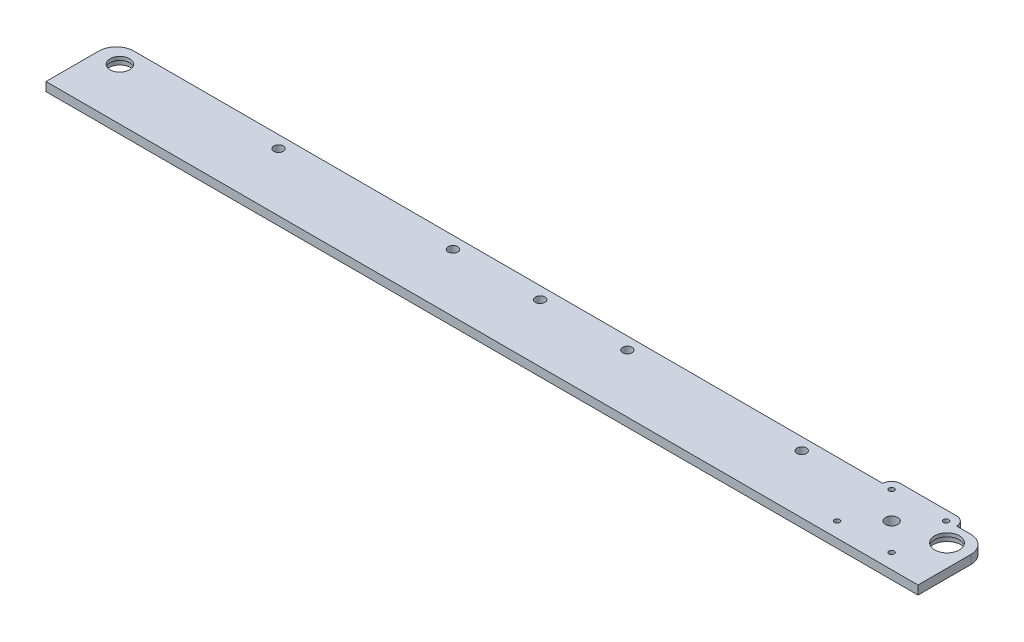
SolidWorks part; units mm, degrees
ref_plane "Front Plane" through (0, 0, 0) normal (0, 0, 1) x (1, 0, 0)
ref_plane "Top Plane" through (0, 0, 0) normal (0, 1, 0) x (1, 0, 0)
ref_plane "Right Plane" through (0, 0, 0) normal (1, 0, 0) x (0, 0, -1)
sketch "Sketch1" plane through (0, 0, 0) normal (0, 1, 0) x (1, 0, 0)
  line L1 (-392.299, 63.778) -> (103.701, 63.778)
  line L2 (-392.299, 63.778) -> (-392.299, 23.778)
  line L3 (-392.299, 23.778) -> (103.701, 23.778)
  line L4 (103.701, 63.778) -> (103.701, 23.778)
  line L8 (-379.799, 53.278) -> (-379.799, 63.778) construction
  line L9 (91.201, 52.778) -> (91.201, 63.778) construction
  line L10 (-144.299, 63.778) -> (-144.299, 183.778) construction
  line L14 (-392.299, 53.278) -> (-392.299, 63.778) construction
  line L15 (-199.299, 183.778) -> (-89.299, 183.778) construction
  line L18 (-392.299, 56.8447) -> (-293.099, 56.8447) construction
  line L20 (-293.099, 56.8447) -> (-193.899, 56.8447) construction
  line L22 (-193.899, 56.8447) -> (-94.699, 56.8447) construction
  line L23 (-94.699, 56.8447) -> (4.501, 56.8447) construction
  line L24 (4.501, 56.8447) -> (103.701, 56.8447) construction
  circle A5 centre (-379.799, 53.278) radius 5.5
  circle A6 centre (91.201, 52.778) radius 7
  circle A10 centre (-293.099, 56.8447) radius 2.7
  circle A11 centre (-193.899, 56.8447) radius 2.7
  circle A12 centre (-94.699, 56.8447) radius 2.7
  circle A13 centre (4.501, 56.8447) radius 2.7
  circle A14 centre (-144.299, 56.8447) radius 2.7
  point P24 (-144.299, 183.778)
  dimension "D5" = 11
  dimension "D6" = 10.5
  dimension "D7" = 11
  dimension "D3" = 12.5
  dimension "D8" = 14
  dimension "D9" = 5.4
  dimension "D10" = 5.4
  dimension "D11" = 99.2
  dimension "D13" = 5.4
  dimension "D4" = 5.4
  dimension "D15" = 5.4
  dimension "D1" = 496
  dimension "D2" = 40
  dimension "D12" = 471.0003
  dimension "D14" = 120
  dimension "D16" = 12.5
extrude "Boss-Extrude1" add sketch "Sketch1" along normal blind 5
sketch "Sketch2" plane through (0, 0, 0) normal (0, -1, 0) x (1, 0, 0)
  circle A0 centre (-379.799, -53.278) radius 6.5
  circle A1 centre (91.201, -52.778) radius 8
  dimension "D1" = 16
  dimension "D2" = 13
extrude "Cut-Extrude1" cut sketch "Sketch2" against normal blind 3
fillet "Fillet1" radius 10 2 edges at (-392.299, 2.5, -63.778) (103.701, 2.5, -63.778)
sketch "Sketch3" plane through (0, 5, 0) normal (0, 1, 0) x (1, 0, 0)
  line L0 (91.201, 52.778) -> (64.668, 47.778) construction
  line L1 (64.668, 47.778) -> (64.668, 26.778) construction
  line L2 (64.668, 26.778) -> (64.668, 23.778) construction
  line L3 (-392.299, 23.778) -> (103.701, 23.778) construction
  line L9 (43.668, 68.778) -> (85.668, 68.778)
  line L10 (43.668, 68.778) -> (43.668, 59.0828)
  line L11 (43.668, 59.0828) -> (85.668, 59.0828)
  line L12 (85.668, 68.778) -> (85.668, 59.0828)
  circle A0 centre (64.668, 47.778) radius 21 construction
  dimension "D1" = 27
  dimension "D2" = 3
  dimension "D3" = 21
extrude "Boss-Extrude2" add sketch "Sketch3" against normal blind 5
sketch "Sketch5" plane through (0, 5, 0) normal (0, 1, 0) x (1, 0, 0)
  line L0 (43.668, 68.778) -> (43.668, 26.778) construction
  line L1 (43.668, 26.778) -> (85.668, 26.778) construction
  line L2 (85.668, 26.778) -> (85.668, 68.778) construction
  line L3 (43.668, 68.778) -> (85.668, 26.778) construction
  line L5 (80.168, 63.278) -> (49.168, 63.278) construction
  line L6 (80.168, 63.278) -> (80.168, 32.278) construction
  line L7 (80.168, 32.278) -> (49.168, 32.278) construction
  line L8 (49.168, 63.278) -> (49.168, 32.278) construction
  circle A0 centre (64.668, 47.778) radius 3.5
  circle A1 centre (64.668, 47.778) radius 15.5 construction
  circle A2 centre (49.168, 63.278) radius 1.5
  circle A3 centre (80.168, 63.278) radius 1.5
  circle A4 centre (80.168, 32.278) radius 1.5
  circle A5 centre (49.168, 32.278) radius 1.5
  dimension "D3" = 31
  dimension "D4" = 7
  dimension "D5" = 3
  dimension "D1" = 42
  dimension "D2" = 42
extrude "Cut-Extrude2" cut sketch "Sketch5" against normal blind 5
fillet "Fillet2" radius 5 2 edges at (43.668, 2.5, -68.778) (85.668, 2.5, -68.778)
sketch "Sketch6" plane through (0, 0, 0) normal (0, -1, 0) x (1, 0, 0)
  circle A0 centre (49.168, -32.278) radius 3
  circle A1 centre (80.168, -32.278) radius 3
  circle A2 centre (49.168, -63.278) radius 3
  circle A3 centre (80.168, -63.278) radius 3
  dimension "D1" = 6
extrude "Cut-Extrude3" cut sketch "Sketch6" against normal blind 2
